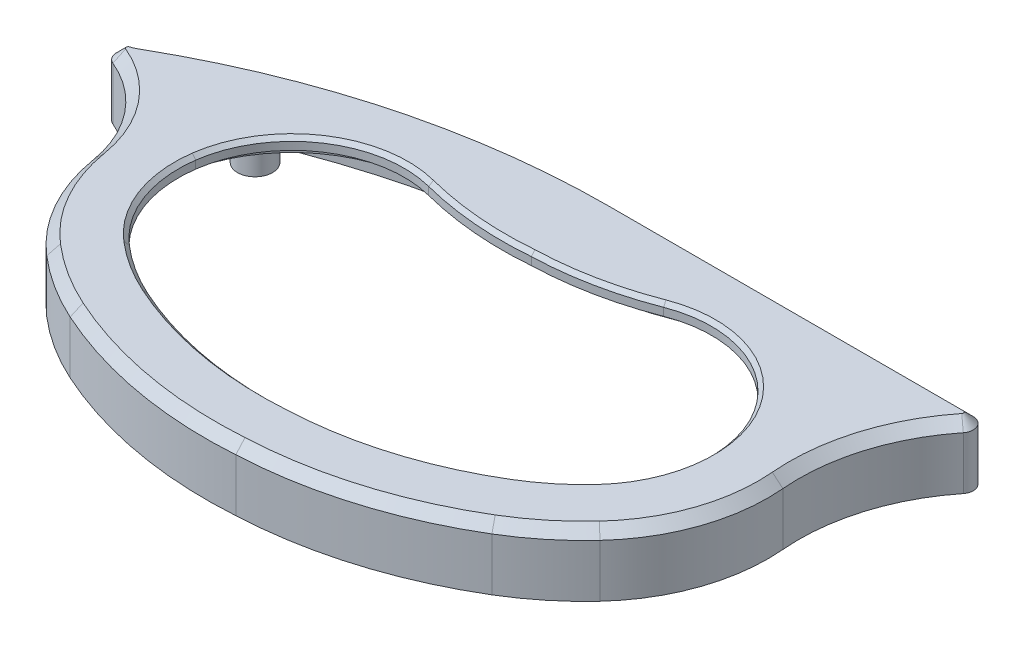
SolidWorks part; units mm, degrees
ref_plane "Front Plane" through (0, 0, 0) normal (0, 0, 1) x (1, 0, 0)
ref_plane "Top Plane" through (0, 0, 0) normal (0, 1, 0) x (1, 0, 0)
ref_plane "Right Plane" through (0, 0, 0) normal (1, 0, 0) x (0, 0, -1)
sketch "Case_Line" plane through (0, 0, 0) normal (0, 1, 0) x (1, 0, 0)
  line L0 (80.0987, 83.4768) -> (-10.614, 83.4768) construction
  arc A0 (85.0987, 88.4768) -> (80.0987, 83.4768) centre (80.0987, 88.4768) cw construction
  arc A2 (-113.6793, 59.6258) -> (-106.8525, 57.7833) centre (-109.3447, 62.1179) ccw construction
  arc A6 (-10.614, 83.4768) -> (-106.8525, 57.7833) centre (-10.614, -109.6066) ccw construction
sketch "Wrest" plane through (0, 0, 0) normal (0, 1, 0) x (1, 0, 0)
  line L6 (-10.569, 65.8598) -> (-6.2316, -9.4162) construction
  line L7 (-10.569, 65.8598) -> (16.1282, 71.2217) construction
  line L8 (16.1282, 71.2217) -> (60.9608, 48.0555) construction
  line L9 (60.9608, 48.0555) -> (52.5888, 15.0143) construction
  line L10 (52.5888, 15.0143) -> (39.5302, 4.389) construction
  line L11 (39.5302, 4.389) -> (-6.2316, -9.4162) construction
  line L14 (80.0987, 83.4768) -> (-10.614, 83.4768) construction
  line L19 (-74.9013, 38.0401) -> (-74.9013, -63.0808) construction
  line L21 (-74.9013, 105.4768) -> (-74.9013, 87.4768) construction
  arc A10 (-10.569, 65.8598) -> (16.1282, 71.2217) centre (-12.89, 146.5605) ccw construction
  arc A11 (16.1282, 71.2217) -> (60.9608, 48.0555) centre (28.2576, 39.7306) cw construction
  arc A12 (60.9608, 48.0555) -> (52.5888, 15.0143) centre (26.348, 39.2445) cw construction
  arc A13 (52.5888, 15.0143) -> (39.5302, 4.389) centre (8.9509, 55.3086) cw construction
  arc A14 (39.5302, 4.389) -> (-6.2316, -9.4162) centre (-10.6307, 87.9151) cw construction
  arc A15 (-53.2763, -0.9584) -> (-6.2316, -9.4162) centre (-13.0408, 87.7763) ccw construction
  arc A16 (-67.4688, 8.0967) -> (-53.2763, -0.9584) centre (-28.7477, 53.1364) ccw construction
  arc A17 (-79.5804, 39.9577) -> (-67.4688, 8.0967) centre (-44.1846, 35.1805) ccw construction
  arc A18 (-37.7053, 68.1198) -> (-79.5804, 39.9577) centre (-46.1374, 35.444) ccw construction
  arc A19 (-10.569, 65.8598) -> (-37.7053, 68.1198) centre (-17.5323, 146.293) cw construction
  arc A20 (12.5339, 80.5534) -> (70.6518, 50.5225) centre (28.2576, 39.7306) cw construction
  arc A24 (-10.2812, 60.8661) -> (17.9253, 66.5558) centre (-12.89, 146.5605) ccw
  arc A50 (70.6518, 50.5225) -> (59.9357, 8.2303) centre (26.348, 39.2445) cw construction
  arc A51 (59.9357, 8.2303) -> (44.6786, -4.1838) centre (8.9509, 55.3086) cw construction
  arc A53 (44.6786, -4.1838) -> (-5.6564, -19.4003) centre (-10.6307, 87.9151) cw construction
  arc A54 (-57.4059, -10.0658) -> (-5.6564, -19.4003) centre (-13.0408, 87.7763) ccw construction
  arc A58 (-73.9879, 0.5138) -> (-57.4059, -10.0658) centre (-28.7477, 53.1364) ccw construction
  arc A71 (17.9253, 66.5558) -> (56.1154, 46.8221) centre (28.2576, 39.7306) cw
  arc A72 (56.1154, 46.8221) -> (48.9153, 18.4063) centre (26.348, 39.2445) cw
  arc A73 (48.9153, 18.4063) -> (36.9561, 8.6755) centre (8.9509, 55.3086) cw
  arc A74 (36.9561, 8.6755) -> (-6.5193, -4.424) centre (-10.6307, 87.9151) cw
  arc A75 (-51.2115, 3.5954) -> (-6.5193, -4.424) centre (-13.0408, 87.7763) ccw
  arc A76 (-64.2092, 11.8882) -> (-51.2115, 3.5954) centre (-28.7477, 53.1364) ccw
  arc A77 (-74.6253, 39.2889) -> (-64.2092, 11.8882) centre (-44.1846, 35.1805) ccw
  arc A78 (-38.9546, 63.2784) -> (-74.6253, 39.2889) centre (-46.1374, 35.444) ccw
  arc A79 (-10.2812, 60.8661) -> (-38.9546, 63.2784) centre (-17.5323, 146.293) cw
  arc A80 (-89.4906, 41.2952) -> (-73.9879, 0.5138) centre (-44.1846, 35.1805) ccw construction
  arc A81 (-35.2066, 77.8026) -> (-89.4906, 41.2952) centre (-46.1374, 35.444) ccw construction
  arc A82 (-11.1445, 75.8479) -> (-35.2066, 77.8026) centre (-17.5323, 146.293) cw construction
  arc A83 (-11.1445, 75.8479) -> (12.5339, 80.5534) centre (-12.89, 146.5605) ccw construction
  arc A85 (-10.614, 83.4768) -> (-106.8525, 57.7833) centre (-10.614, -109.6066) ccw construction
  dimension "D2" = 27.2303
  dimension "D7" = 80.7341
  dimension "D15" = 5
  dimension "D1" = 75.4008
  dimension "D3" = 50.4642
  dimension "D4" = 34.0854
  dimension "D5" = 47.7989
  dimension "D6" = 16.8352
  dimension "D8" = 103.108
  dimension "D9" = 98.059
  dimension "D10" = 76.51
  dimension "D11" = 10
sketch "Sketch6" plane through (0, 0, 0) normal (0, 1, 0) x (1, 0, 0)
  line L0 (84.9594, 87.3051) -> (70.7917, 28.5311) construction
  line L1 (-88.1859, 17.3185) -> (-113.6272, 59.5372) construction
  line L2 (80.0987, 83.4768) -> (-10.614, 83.4768)
  arc A0 (-73.9879, 0.5138) -> (-57.4059, -10.0658) centre (-28.7477, 53.1364) ccw construction
  arc A1 (59.9357, 8.2303) -> (70.6518, 50.5225) centre (26.348, 39.2445) ccw construction
  arc A2 (-113.6793, 59.6258) -> (-106.8525, 57.7833) centre (-109.3447, 62.1179) ccw construction
  arc A3 (80.0987, 83.4768) -> (85.0987, 88.4768) centre (80.0987, 88.4768) ccw construction
  arc A4 (80.1793, 83.4775) -> (82.5748, 78.6094) centre (80.2278, 80.4779) cw
  arc A5 (-107.9166, 57.3262) -> (-108.2193, 51.6843) centre (-107.0597, 54.4512) ccw
  circle A6 centre (80.2278, 80.4779) radius 3 construction
  arc A7 (-5.6564, -19.4003) -> (44.6786, -4.1838) centre (-10.6307, 87.9151) ccw construction
  arc A8 (59.9357, 8.2303) -> (71.8718, 43.1263) centre (26.4104, 39.1869) ccw
  arc A9 (82.5748, 78.6094) -> (71.8718, 43.1263) centre (121.7206, 47.4458) ccw
  circle A10 centre (-107.0597, 54.4512) radius 3 construction
  arc A11 (-57.4059, -10.0658) -> (-5.6564, -19.4003) centre (-13.0408, 87.7763) ccw construction
  arc A12 (-108.2193, 51.6843) -> (-89.2905, 27.7324) centre (-120.4115, 22.5936) cw
  arc A13 (-89.4906, 41.2952) -> (-73.9879, 0.5138) centre (-44.1846, 35.1805) ccw construction
  arc A14 (-73.9879, 0.5138) -> (-89.2905, 27.7324) centre (-44.1846, 35.1805) cw
  arc A15 (-73.9879, 0.5138) -> (-57.4059, -10.0658) centre (-28.7477, 53.1364) ccw
  arc A16 (80.1793, 83.4775) -> (80.0987, 83.4768) centre (80.0987, 88.4768) cw
  arc A21 (-57.4059, -10.0658) -> (-5.6564, -19.4003) centre (-13.0408, 87.7763) ccw
  arc A22 (59.9357, 8.2303) -> (44.6786, -4.1838) centre (8.9509, 55.3086) cw
  arc A23 (44.6786, -4.1838) -> (-5.6564, -19.4003) centre (-10.6307, 87.9151) cw
  arc A24 (70.6518, 50.5225) -> (12.5339, 80.5534) centre (28.2576, 39.7306) ccw construction
  arc A25 (-107.9166, 57.3262) -> (-106.8525, 57.7833) centre (-109.3447, 62.1179) ccw
  arc A26 (-106.8525, 57.7833) -> (-10.614, 83.4768) centre (-10.614, -109.6066) cw
  dimension "D1" = 3
extrude "Top_plane" add sketch "Sketch6" against normal blind 3
sketch "Sketch9" plane through (0, 0, 0) normal (0, 1, 0) x (1, 0, 0)
  arc A20 (-10.2812, 60.8661) -> (17.9253, 66.5558) centre (-12.89, 146.5605) ccw
  arc A21 (56.1154, 46.8221) -> (17.9253, 66.5558) centre (28.2576, 39.7306) ccw
  arc A22 (48.9153, 18.4063) -> (56.1154, 46.8221) centre (26.348, 39.2445) ccw
  arc A23 (36.9561, 8.6755) -> (48.9153, 18.4063) centre (8.9509, 55.3086) ccw
  arc A24 (-6.5193, -4.424) -> (36.9561, 8.6755) centre (-10.6307, 87.9151) ccw
  arc A25 (-51.2115, 3.5954) -> (-6.5193, -4.424) centre (-13.0408, 87.7763) ccw
  arc A26 (-64.2092, 11.8882) -> (-51.2115, 3.5954) centre (-28.7477, 53.1364) ccw
  arc A27 (-74.6253, 39.2889) -> (-64.2092, 11.8882) centre (-44.1846, 35.1805) ccw
  arc A28 (-38.9546, 63.2784) -> (-74.6253, 39.2889) centre (-46.1374, 35.444) ccw
  arc A29 (-38.9546, 63.2784) -> (-10.2812, 60.8661) centre (-17.5323, 146.293) ccw
  arc A30 (-10.2812, 60.8661) -> (17.9253, 66.5558) centre (-12.89, 146.5605) ccw
  arc A31 (56.1154, 46.8221) -> (17.9253, 66.5558) centre (28.2576, 39.7306) ccw
  arc A32 (48.9153, 18.4063) -> (56.1154, 46.8221) centre (26.348, 39.2445) ccw
  arc A33 (36.9561, 8.6755) -> (48.9153, 18.4063) centre (8.9509, 55.3086) ccw
  arc A34 (-6.5193, -4.424) -> (36.9561, 8.6755) centre (-10.6307, 87.9151) ccw
  arc A35 (-51.2115, 3.5954) -> (-6.5193, -4.424) centre (-13.0408, 87.7763) ccw
  arc A36 (-64.2092, 11.8882) -> (-51.2115, 3.5954) centre (-28.7477, 53.1364) ccw
  arc A37 (-74.6253, 39.2889) -> (-64.2092, 11.8882) centre (-44.1846, 35.1805) ccw
  arc A38 (-38.9546, 63.2784) -> (-74.6253, 39.2889) centre (-46.1374, 35.444) ccw
  arc A39 (-38.9546, 63.2784) -> (-10.2812, 60.8661) centre (-17.5323, 146.293) ccw
  dimension "D1" = 0
extrude "Pillow_hole" cut sketch "Sketch9" against normal through all
chamfer "Pillow_chamfer" distance 1 angle 45 10 edges at (16.0353, 0, 0.5854) (43.2822, 0, -13.115) (56.1237, 0, -31.6999) (4.0625, 0, -62.5191) (41.4538, 0, -65.2689) (-29.3655, 0, 3.2014) (-58.0057, 0, -7.2789) (-24.7198, 0, -60.8607) (-72.8968, 0, -24.2659) (-62.1796, 0, -59.2977)
sketch "Sketch7" plane through (0, -3, 0) normal (0, -1, 0) x (1, 0, 0)
  line L3 (-10.614, -83.4768) -> (80.0987, -83.4768)
  line L4 (-10.614, -83.4768) -> (80.0987, -83.4768)
  arc A37 (-106.8525, -57.7833) -> (-10.614, -83.4768) centre (-10.614, 109.6066) ccw
  arc A38 (-106.8525, -57.7833) -> (-107.9166, -57.3262) centre (-109.3447, -62.1179) ccw
  arc A39 (-108.2193, -51.6843) -> (-107.9166, -57.3262) centre (-107.0597, -54.4512) ccw
  arc A40 (-108.2193, -51.6843) -> (-89.2905, -27.7324) centre (-120.4115, -22.5936) ccw
  arc A41 (-73.9879, -0.5138) -> (-89.2905, -27.7324) centre (-44.1846, -35.1805) ccw
  arc A42 (-57.4059, 10.0658) -> (-73.9879, -0.5138) centre (-28.7477, -53.1364) ccw
  arc A43 (-5.6564, 19.4003) -> (-57.4059, 10.0658) centre (-13.0408, -87.7763) ccw
  arc A44 (44.6786, 4.1838) -> (-5.6564, 19.4003) centre (-10.6307, -87.9151) ccw
  arc A45 (59.9357, -8.2303) -> (44.6786, 4.1838) centre (8.9509, -55.3086) ccw
  arc A46 (71.8718, -43.1263) -> (59.9357, -8.2303) centre (26.4104, -39.1869) ccw
  arc A47 (71.8718, -43.1263) -> (82.5748, -78.6094) centre (121.7206, -47.4458) ccw
  arc A48 (80.1793, -83.4775) -> (82.5748, -78.6094) centre (80.2278, -80.4779) ccw
  arc A49 (80.1793, -83.4775) -> (80.0987, -83.4768) centre (80.0987, -88.4768) ccw
  arc A50 (-106.8525, -57.7833) -> (-10.614, -83.4768) centre (-10.614, 109.6066) ccw
  arc A51 (-106.8525, -57.7833) -> (-107.9166, -57.3262) centre (-109.3447, -62.1179) ccw
  arc A52 (-108.2193, -51.6843) -> (-107.9166, -57.3262) centre (-107.0597, -54.4512) ccw
  arc A53 (-108.2193, -51.6843) -> (-89.2905, -27.7324) centre (-120.4115, -22.5936) ccw
  arc A54 (-73.9879, -0.5138) -> (-89.2905, -27.7324) centre (-44.1846, -35.1805) ccw
  arc A55 (-57.4059, 10.0658) -> (-73.9879, -0.5138) centre (-28.7477, -53.1364) ccw
  arc A56 (-5.6564, 19.4003) -> (-57.4059, 10.0658) centre (-13.0408, -87.7763) ccw
  arc A57 (44.6786, 4.1838) -> (-5.6564, 19.4003) centre (-10.6307, -87.9151) ccw
  arc A58 (59.9357, -8.2303) -> (44.6786, 4.1838) centre (8.9509, -55.3086) ccw
  arc A59 (71.8718, -43.1263) -> (59.9357, -8.2303) centre (26.4104, -39.1869) ccw
  arc A60 (71.8718, -43.1263) -> (82.5748, -78.6094) centre (121.7206, -47.4458) ccw
  arc A61 (80.1793, -83.4775) -> (82.5748, -78.6094) centre (80.2278, -80.4779) ccw
  arc A62 (80.1793, -83.4775) -> (80.0987, -83.4768) centre (80.0987, -88.4768) ccw
  arc A188 (-53.2763, 0.9584) -> (-67.4688, -8.0967) centre (-28.7477, -53.1364) ccw
  arc A189 (-6.2316, 9.4162) -> (-53.2763, 0.9584) centre (-13.0408, -87.7763) ccw
  arc A190 (39.5302, -4.389) -> (-6.2316, 9.4162) centre (-10.6307, -87.9151) ccw
  arc A191 (52.5888, -15.0143) -> (39.5302, -4.389) centre (8.9509, -55.3086) ccw
  arc A192 (60.9608, -48.0555) -> (52.5888, -15.0143) centre (26.348, -39.2445) ccw
  arc A193 (16.1282, -71.2217) -> (60.9608, -48.0555) centre (28.2576, -39.7306) ccw
  arc A194 (16.1282, -71.2217) -> (-10.569, -65.8598) centre (-12.89, -146.5605) ccw
  arc A195 (-10.569, -65.8598) -> (-37.7053, -68.1198) centre (-17.5323, -146.293) ccw
  arc A196 (-79.5804, -39.9577) -> (-37.7053, -68.1198) centre (-46.1374, -35.444) ccw
  arc A197 (-67.4688, -8.0967) -> (-79.5804, -39.9577) centre (-44.1846, -35.1805) ccw
  arc A198 (-53.2763, 0.9584) -> (-67.4688, -8.0967) centre (-28.7477, -53.1364) ccw
  arc A199 (-6.2316, 9.4162) -> (-53.2763, 0.9584) centre (-13.0408, -87.7763) ccw
  arc A200 (39.5302, -4.389) -> (-6.2316, 9.4162) centre (-10.6307, -87.9151) ccw
  arc A201 (52.5888, -15.0143) -> (39.5302, -4.389) centre (8.9509, -55.3086) ccw
  arc A202 (60.9608, -48.0555) -> (52.5888, -15.0143) centre (26.348, -39.2445) ccw
  arc A203 (16.1282, -71.2217) -> (60.9608, -48.0555) centre (28.2576, -39.7306) ccw
  arc A204 (16.1282, -71.2217) -> (-10.569, -65.8598) centre (-12.89, -146.5605) ccw
  arc A205 (-10.569, -65.8598) -> (-37.7053, -68.1198) centre (-17.5323, -146.293) ccw
  arc A206 (-79.5804, -39.9577) -> (-37.7053, -68.1198) centre (-46.1374, -35.444) ccw
  arc A207 (-67.4688, -8.0967) -> (-79.5804, -39.9577) centre (-44.1846, -35.1805) ccw
  dimension "D1" = 0
  dimension "D2" = 0
extrude "Wrest_socket" add sketch "Sketch7" along normal blind 4
sketch "Sketch8" plane through (0, -7, 0) normal (0, -1, 0) x (1, 0, 0)
  line L2 (-10.614, -81.4768) -> (80.0987, -81.4768)
  line L6 (-10.614, -83.4768) -> (80.0987, -83.4768)
  line L7 (-10.614, -83.4768) -> (80.0987, -83.4768)
  arc A45 (80.2116, -81.4778) -> (80.0987, -81.4768) centre (80.0987, -88.4768) ccw
  arc A46 (80.2116, -81.4778) -> (81.0101, -79.8551) centre (80.2278, -80.4779) ccw
  arc A47 (69.8793, -42.9536) -> (81.0101, -79.8551) centre (121.7206, -47.4458) ccw
  arc A48 (69.8793, -42.9536) -> (58.4664, -9.5871) centre (26.4104, -39.1869) ccw
  arc A49 (58.4664, -9.5871) -> (43.6489, 2.4693) centre (8.9509, -55.3086) ccw
  arc A50 (43.6489, 2.4693) -> (-5.7714, 17.4035) centre (-10.6307, -87.9151) ccw
  arc A51 (-5.7714, 17.4035) -> (-56.58, 8.2443) centre (-13.0408, -87.7763) ccw
  arc A52 (-56.58, 8.2443) -> (-72.6841, -2.0304) centre (-28.7477, -53.1364) ccw
  arc A53 (-72.6841, -2.0304) -> (-87.3173, -28.0582) centre (-44.1846, -35.1805) ccw
  arc A54 (-107.4463, -53.5289) -> (-87.3173, -28.0582) centre (-120.4115, -22.5936) ccw
  arc A55 (-107.4463, -53.5289) -> (-107.3453, -55.4095) centre (-107.0597, -54.4512) ccw
  arc A56 (-105.8557, -56.0494) -> (-107.3453, -55.4095) centre (-109.3447, -62.1179) ccw
  arc A57 (-105.8557, -56.0494) -> (-10.614, -81.4768) centre (-10.614, 109.6066) ccw
  arc A58 (-106.8525, -57.7833) -> (-10.614, -83.4768) centre (-10.614, 109.6066) ccw
  arc A59 (-106.8525, -57.7833) -> (-107.9166, -57.3262) centre (-109.3447, -62.1179) ccw
  arc A60 (-108.2193, -51.6843) -> (-107.9166, -57.3262) centre (-107.0597, -54.4512) ccw
  arc A61 (-108.2193, -51.6843) -> (-89.2905, -27.7324) centre (-120.4115, -22.5936) ccw
  arc A62 (-73.9879, -0.5138) -> (-89.2905, -27.7324) centre (-44.1846, -35.1805) ccw
  arc A63 (-57.4059, 10.0658) -> (-73.9879, -0.5138) centre (-28.7477, -53.1364) ccw
  arc A64 (-5.6564, 19.4003) -> (-57.4059, 10.0658) centre (-13.0408, -87.7763) ccw
  arc A65 (44.6786, 4.1838) -> (-5.6564, 19.4003) centre (-10.6307, -87.9151) ccw
  arc A66 (59.9357, -8.2303) -> (44.6786, 4.1838) centre (8.9509, -55.3086) ccw
  arc A67 (71.8718, -43.1263) -> (59.9357, -8.2303) centre (26.4104, -39.1869) ccw
  arc A68 (71.8718, -43.1263) -> (82.5748, -78.6094) centre (121.7206, -47.4458) ccw
  arc A69 (80.1793, -83.4775) -> (82.5748, -78.6094) centre (80.2278, -80.4779) ccw
  arc A70 (80.1793, -83.4775) -> (80.0987, -83.4768) centre (80.0987, -88.4768) ccw
  arc A71 (-106.8525, -57.7833) -> (-10.614, -83.4768) centre (-10.614, 109.6066) ccw
  arc A72 (-106.8525, -57.7833) -> (-107.9166, -57.3262) centre (-109.3447, -62.1179) ccw
  arc A73 (-108.2193, -51.6843) -> (-107.9166, -57.3262) centre (-107.0597, -54.4512) ccw
  arc A74 (-108.2193, -51.6843) -> (-89.2905, -27.7324) centre (-120.4115, -22.5936) ccw
  arc A75 (-73.9879, -0.5138) -> (-89.2905, -27.7324) centre (-44.1846, -35.1805) ccw
  arc A76 (-57.4059, 10.0658) -> (-73.9879, -0.5138) centre (-28.7477, -53.1364) ccw
  arc A77 (-5.6564, 19.4003) -> (-57.4059, 10.0658) centre (-13.0408, -87.7763) ccw
  arc A78 (44.6786, 4.1838) -> (-5.6564, 19.4003) centre (-10.6307, -87.9151) ccw
  arc A79 (59.9357, -8.2303) -> (44.6786, 4.1838) centre (8.9509, -55.3086) ccw
  arc A80 (71.8718, -43.1263) -> (59.9357, -8.2303) centre (26.4104, -39.1869) ccw
  arc A81 (71.8718, -43.1263) -> (82.5748, -78.6094) centre (121.7206, -47.4458) ccw
  arc A82 (80.1793, -83.4775) -> (82.5748, -78.6094) centre (80.2278, -80.4779) ccw
  arc A83 (80.1793, -83.4775) -> (80.0987, -83.4768) centre (80.0987, -88.4768) ccw
  dimension "D1" = 0
  dimension "D2" = 2
extrude "Wall" add sketch "Sketch8" along normal blind 9
chamfer "Main_chamfer" distance 2.5 angle 45 14 edges at (-110.0554, 0, -54.6119) (-32.1111, 0, 17.9482) (20.4565, 0, 14.9193) (52.7492, 0, -1.4799) (82.9195, 0, -81.8024) (80.139, 0, -83.477) (34.7423, 0, -83.4768) (-95.6642, 0, -42.1509) (-84.0351, 0, -12.7761) (-66.0737, 0, 5.3665) (69.5863, 0, -24.4187) (73.8168, 0, -61.8954) (-60.4187, 0, -76.9429) (-107.3713, 0, -57.5238)
sketch "Sketch10" plane through (0, -7, 0) normal (0, -1, 0) x (1, 0, 0)
  line L0 (-10.2812, -60.8661) -> (-6.5193, 4.424) construction
  line L1 (-78, -57.8598) -> (-8.4002, -28.221) construction
  line L2 (-8.4002, -28.221) -> (47.5551, -4.3927) construction
  circle A0 centre (-78, -57.8598) radius 4.5
  circle A1 centre (-78, -57.8598) radius 1.35
  circle A2 centre (47.5551, -4.3927) radius 4.5
  circle A3 centre (47.5551, -4.3927) radius 1.35
  arc A5 (52.5888, -15.0143) -> (39.5302, -4.389) centre (8.9509, -55.3086) ccw construction
  dimension "D1" = 9
  dimension "D2" = 2.7
  dimension "D3" = 78
  dimension "D4" = 8
extrude "Boss-Extrude1" add sketch "Sketch10" along normal blind 5.5
sketch "Sketch13" plane through (0, -12.5, 0) normal (0, -1, 0) x (1, 0, 0)
  line L1 (-76.4989, -60.4598) -> (-74.9978, -57.8598)
  line L2 (-74.9978, -57.8598) -> (-76.4989, -55.2598)
  line L3 (-76.4989, -55.2598) -> (-79.5011, -55.2598)
  line L4 (-79.5011, -55.2598) -> (-81.0022, -57.8598)
  line L5 (-81.0022, -57.8598) -> (-79.5011, -60.4598)
  line L6 (-79.5011, -60.4598) -> (-76.4989, -60.4598)
  line L7 (49.0562, -6.9927) -> (50.5573, -4.3927)
  line L8 (50.5573, -4.3927) -> (49.0562, -1.7927)
  line L9 (49.0562, -1.7927) -> (46.054, -1.7927)
  line L10 (46.054, -1.7927) -> (44.5529, -4.3927)
  line L11 (44.5529, -4.3927) -> (46.054, -6.9927)
  line L12 (46.054, -6.9927) -> (49.0562, -6.9927)
  circle A0 centre (-78, -57.8598) radius 2.6 construction
  circle A1 centre (47.5551, -4.3927) radius 2.6 construction
  dimension "D1" = 5.2
extrude "Nut_holes" cut sketch "Sketch13" against normal blind 3
ref_plane "Magnet01-Plane1" through (-51.514, 0, -89.5994) normal (-0.4984, 0, -0.8669) x (-0.8669, 0, 0.4984)
ref_plane "Magnet01-Plane2" through (-50.5171, 0, -87.8656) normal (0.4984, 0, 0.8669) x (0.8669, 0, -0.4984)
sketch "Sketch11" plane through (-50.5171, 0, -87.8656) normal (0.4984, 0, 0.8669) x (0.8669, 0, -0.4984)
  line L0 (-63.8328, -16) -> (-63.8328, -2.5) construction
  line L2 (-63.8328, -16) -> (32.4057, -16) construction
  circle A0 centre (-53.8328, -7.5) radius 3
  dimension "D3" = 6
  dimension "D1" = 10
  dimension "D2" = 8.5
extrude "Magnet01" cut sketch "Sketch11" along normal blind 5.2 and the other way blind 0.5 contours A0
sketch "Sketch12" plane through (0, 0, -81.4768) normal (0, 0, -1) x (-1, 0, 0)
  line L1 (-80.0987, -16) -> (-80.0987, -2.5) construction
  line L2 (10.614, -16) -> (-80.0987, -16) construction
  circle A0 centre (-70.0987, -7.5) radius 3
  dimension "D1" = 6
  dimension "D2" = 8.5
  dimension "D3" = 10
extrude "Magnet02" cut sketch "Sketch12" against normal blind 5.2 and the other way blind 0.5
